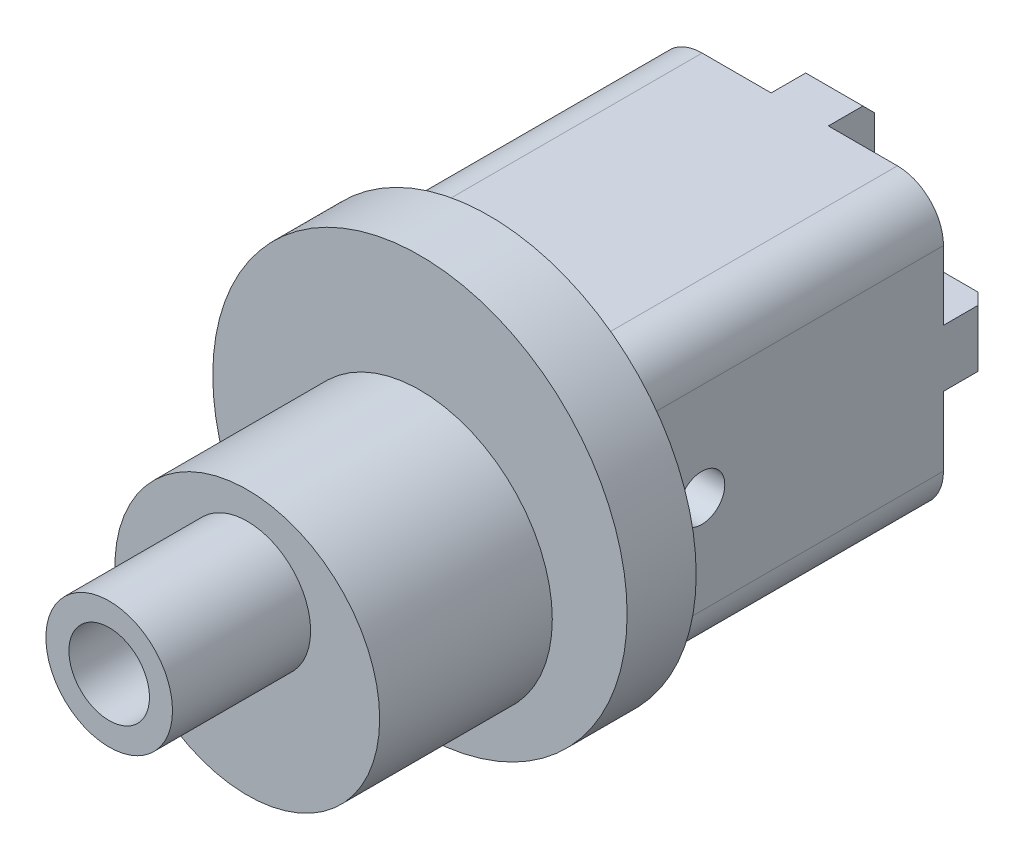
SolidWorks part; units mm, degrees
material "ABS PC"
ref_plane "Front Plane" through (0, 0, 0) normal (0, 0, 1) x (1, 0, 0)
ref_plane "Top Plane" through (0, 0, 0) normal (0, 1, 0) x (1, 0, 0)
ref_plane "Right Plane" through (0, 0, 0) normal (1, 0, 0) x (0, 0, -1)
sketch "Sketch1" plane through (0, 0, 0) normal (0, 0, 1) x (1, 0, 0)
  line L0 (4.2426, 6.2426) -> (-4.2426, 6.2426)
  line L1 (6.2426, 4.2426) -> (6.2426, -4.2426)
  line L2 (4.2426, -6.2426) -> (-4.2426, -6.2426)
  line L3 (-6.2426, 4.2426) -> (-6.2426, -4.2426)
  line L4 (2.2426, 4.2426) -> (2.2426, 6.2426)
  line L5 (4.2426, 2.2426) -> (6.2426, 2.2426)
  line L6 (4.2426, -2.2426) -> (6.2426, -2.2426)
  line L7 (2.2426, -4.2426) -> (2.2426, -6.2426)
  line L8 (-2.2426, -4.2426) -> (-2.2426, -6.2426)
  line L9 (-4.2426, -2.2426) -> (-6.2426, -2.2426)
  line L10 (-4.2426, 2.2426) -> (-6.2426, 2.2426)
  line L11 (-2.2426, 4.2426) -> (-2.2426, 6.2426)
  line L12 (1.2426, 4.2426) -> (1.2426, 6.2426)
  line L13 (4.2426, 1.2426) -> (6.2426, 1.2426)
  line L14 (4.2426, -1.2426) -> (6.2426, -1.2426)
  line L15 (1.2426, -4.2426) -> (1.2426, -6.2426)
  line L16 (-1.2426, -4.2426) -> (-1.2426, -6.2426)
  line L17 (-4.2426, -1.2426) -> (-6.2426, -1.2426)
  line L18 (-4.2426, 1.2426) -> (-6.2426, 1.2426)
  line L19 (-1.2426, 4.2426) -> (-1.2426, 6.2426)
  line L20 (0, 7.8016) -> (0, -8.0944) construction
  line L21 (-8.9739, 0) -> (10.2388, 0) construction
  circle A0 centre (-4.2426, 4.2426) radius 2
  circle A4 centre (4.2426, 4.2426) radius 2
  circle A5 centre (4.2426, -4.2426) radius 2
  circle A6 centre (-4.2426, -4.2426) radius 2
  arc A7 (1.2426, 4.2426) -> (4.2426, 1.2426) centre (4.2426, 4.2426) ccw
  arc A8 (4.2426, -1.2426) -> (1.2426, -4.2426) centre (4.2426, -4.2426) ccw
  arc A9 (-1.2426, -4.2426) -> (-4.2426, -1.2426) centre (-4.2426, -4.2426) ccw
  arc A10 (-4.2426, 1.2426) -> (-1.2426, 4.2426) centre (-4.2426, 4.2426) ccw
  point P13 (0, 0)
  point P55 (0, 0)
  dimension "D1" = 4
  dimension "D3" = 4
  dimension "D2" = 4
sketch "Sketch3" plane through (0, 0, 10) normal (0, 0, 1) x (1, 0, 0)
  circle A0 centre (0, 0) radius 9
  dimension "D1" = 18
extrude "Boss-Extrude3" add sketch "Sketch3" along normal blind 3 from offset 5.5
sketch "Sketch4" plane through (0, 0, 18.5) normal (0, 0, 1) x (1, 0, 0)
  circle A0 centre (0, -1.812) radius 5.75
  dimension "D1" = 11.5
  dimension "D2" = 1.812
extrude "Boss-Extrude4" add sketch "Sketch4" along normal blind 7.5
sketch "Sketch5" plane through (0, 0, 26) normal (0, 0, 1) x (1, 0, 0)
  circle A0 centre (0, 0) radius 2.75
  dimension "D1" = 5.5
extrude "Boss-Extrude5" add sketch "Sketch5" along normal blind 6
extrude "Boss-Extrude8" add sketch "Sketch1" along normal blind 2 separate body contours A10 L18 L3 L17 A9 L16 L2 L15 A8 L14 L1 L13 A7 L12 L0 L19 region at (0, 0, 0)
extrude "Boss-Extrude9" add sketch "Sketch1<7>" along normal blind 13.5 from offset 2 contours A10 L18 L3 L17 A9 L16 L2 L15 A8 L14 L1 L13 A7 L12 L0 L19 | L18 A10 L19 L0 L11 A0 L10 L3 | L12 A7 L13 L1 L5 A4 L4 L0 | L14 A8 L15 L2 L7 A5 L6 L1 | L16 A9 L17 L3 L9 A6 L8 L2 | A6 L9 L3 | A6 | A6 L2 L8 | A5 L7 L2 | A5 | A5 L1 L6 | A4 | A4 L5 L1 | A4 L0 L4 | A0 L11 L0 | A0 | A0 L3 L10 | A4 region at (2.6894, 5.7959, 0) region at (4.2426, 4.2426, 0) region at (2.1719, 5.2426, 0) region at (5.7959, 2.6894, 0) region at (0, 0, 0) region at (-1.3134, 5.2426, 0) region at (-2.6894, 5.7959, 0) region at (6.1719, -1.7426, 0) region at (-4.2426, 4.2426, 0) region at (5.7959, -2.6894, 0) region at (-5.7959, 2.6894, 0) region at (4.2426, -4.2426, 0) region at (-5.2426, -1.3134, 0) region at (2.6894, -5.7959, 0) region at (-5.7959, -2.6894, 0) region at (-4.2426, -4.2426, 0) region at (-2.6894, -5.7959, 0)
sketch "Sketch1<7>" plane through (0, 0, 0) normal (0, 0, 1) x (1, 0, 0) same geometry as "Sketch1"
sketch "Sketch6" plane through (6.2426, 0, 0) normal (1, 0, 0) x (0, 0, -1)
  line L0 (-15.5, 4.2426) -> (-15.5, -4.2426) construction
  circle A0 centre (-12.5, 0) radius 1
  dimension "D1" = 2
  dimension "D2" = 3
extrude "Cut-Extrude1" cut sketch "Sketch6" against normal blind 15
chamfer "Chamfer1" distance 0.5 angle 45 4 edges at (0, -6.2426, 0) (6.2426, 0, 0) (-6.2426, 0, 0) (0, 6.2426, 0)
sketch "Sketch7" plane through (0, 0, 32) normal (0, 0, 1) x (1, 0, 0)
  circle A0 centre (0, 0) radius 1.75
  dimension "D1" = 3.5
extrude "Cut-Extrude2" cut sketch "Sketch7" against normal blind 15
